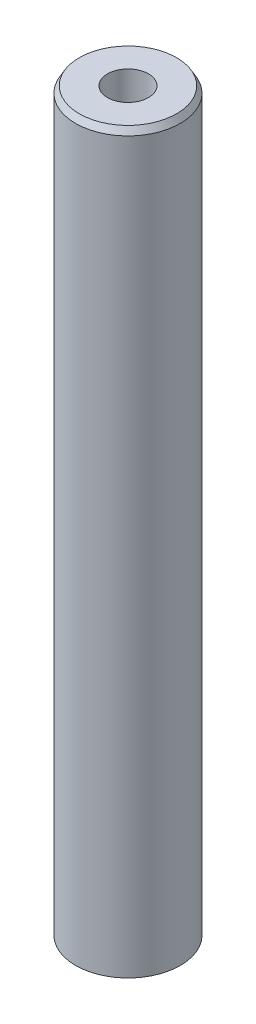
SolidWorks part; units mm, degrees
ref_plane "Front Plane" through (0, 0, 0) normal (0, 0, 1) x (1, 0, 0)
ref_plane "Top Plane" through (0, 0, 0) normal (0, 1, 0) x (1, 0, 0)
ref_plane "Right Plane" through (0, 0, 0) normal (1, 0, 0) x (0, 0, -1)
sketch "Sketch1" plane through (0, 0, 0) normal (0, 1, 0) x (1, 0, 0)
  circle A0 centre (0, 0) radius 42.5
  dimension "SHAFT_OD" = 85
extrude "Boss-Extrude1" add sketch "Sketch1" along normal blind 600
sketch "Sketch2" plane through (0, 0, 0) normal (0, 1, 0) x (1, 0, 0)
  circle A0 centre (0, 0) radius 16.6774
  dimension "BORE_D" = 33.3547
extrude "Cut-Extrude1" cut sketch "Sketch2" along normal through all
chamfer "Chamfer1" distance 5.2593 angle 30 2 edges at (0, 600, 42.5) (0, 0, 42.5) first distance on face at (0, 600, 42.5) first distance on face at (0, 0, 16.6774)
